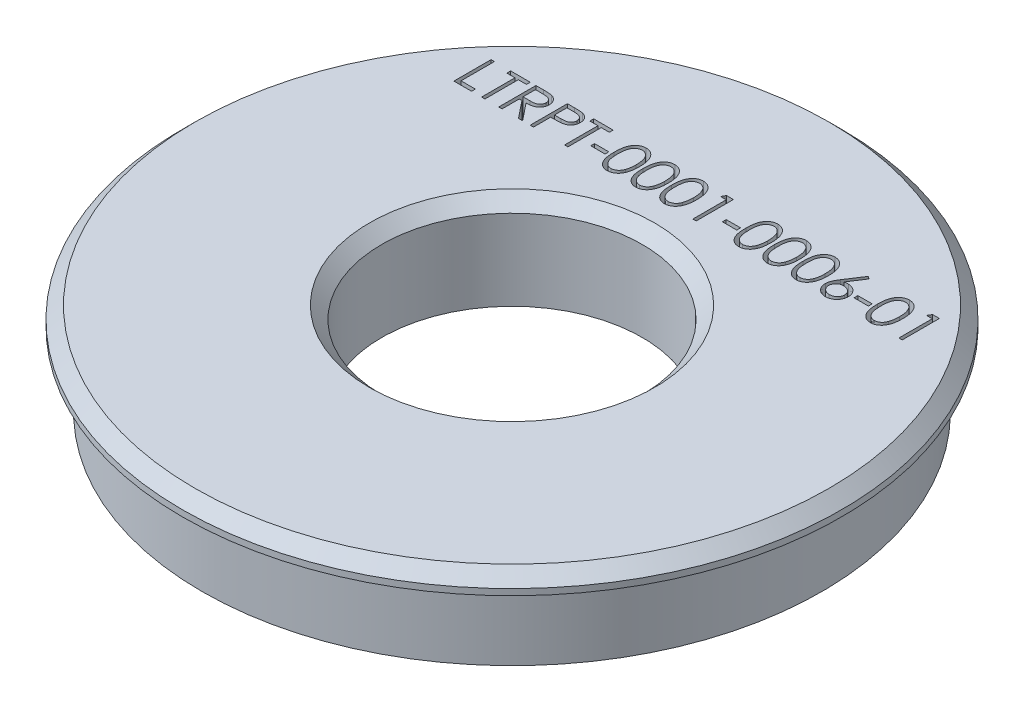
SolidWorks part; units mm, degrees
ref_plane "Front Plane" through (0, 0, 0) normal (0, 0, 1) x (1, 0, 0)
ref_plane "Top Plane" through (0, 0, 0) normal (0, 1, 0) x (1, 0, 0)
ref_plane "Right Plane" through (0, 0, 0) normal (1, 0, 0) x (0, 0, -1)
sketch "Sketch1" plane through (0, 0, 0) normal (0, 1, 0) x (1, 0, 0)
  circle A0 centre (0, 0) radius 25
  dimension "D1" = 50
extrude "Boss-Extrude1" add sketch "Sketch1" along normal blind 6
sketch "Sketch2" plane through (0, 6, 0) normal (0, 1, 0) x (1, 0, 0)
  circle A0 centre (0, 0) radius 10.5
  dimension "D1" = 21
extrude "Cut-Extrude1" cut sketch "Sketch2" against normal up to next
sketch "Sketch3" plane through (0, 6, 0) normal (0, 1, 0) x (1, 0, 0)
  circle A0 centre (0, 0) radius 19 construction
  circle A1 centre (0, 19) radius 2.5
  circle A2 centre (16.4545, 9.5) radius 2.5
  circle A3 centre (16.4545, -9.5) radius 2.5
  circle A4 centre (0, -19) radius 2.5
  circle A5 centre (-16.4545, -9.5) radius 2.5
  circle A6 centre (-16.4545, 9.5) radius 2.5
  point P17 (0, 0)
  dimension "D1" = 38
  dimension "D2" = 5
  dimension "D3" = 6
extrude "Cut-Extrude2" cut sketch "Sketch3" against normal through all
ref_axis "Axis1" through (0, 0, 0) along (0, 1, 0)
sketch "Sketch5" plane through (0, 6, 0) normal (0, 1, 0) x (1, 0, 0)
  circle A0 centre (0, 0) radius 20 construction
  circle A1 centre (20, 0) radius 1.25
  circle A2 centre (10, -17.3205) radius 1.25
  circle A3 centre (-10, -17.3205) radius 1.25
  circle A4 centre (-20, 0) radius 1.25
  circle A5 centre (-10, 17.3205) radius 1.25
  circle A6 centre (10, 17.3205) radius 1.25
  point P18 (0, 0)
  dimension "D1" = 40
  dimension "D2" = 2.5
  dimension "D3" = 6
extrude "Cut-Extrude3" cut sketch "Sketch5" against normal blind 4
sketch "Sketch6" plane through (0, 6, 0) normal (0, 1, 0) x (1, 0, 0)
  circle A0 centre (0, 0) radius 26.5767
  circle A1 centre (0, 0) radius 10.5 construction
  circle A2 centre (0, 0) radius 10.5
  circle A3 centre (10, -17.3205) radius 1.25 construction
  circle A4 centre (10, -17.3205) radius 1.25
  circle A5 centre (-10, -17.3205) radius 1.25 construction
  circle A6 centre (-10, -17.3205) radius 1.25
  circle A7 centre (-20, 0) radius 1.25 construction
  circle A8 centre (-10, 17.3205) radius 1.25 construction
  circle A9 centre (10, 17.3205) radius 1.25 construction
  circle A10 centre (20, 0) radius 1.25 construction
  circle A11 centre (-20, 0) radius 1.25
  circle A12 centre (-10, 17.3205) radius 1.25
  circle A13 centre (10, 17.3205) radius 1.25
  circle A14 centre (20, 0) radius 1.25
extrude "Boss-Extrude2" add sketch "Sketch6" along normal blind 1.5
sketch "Sketch7" plane through (0, 7.5, 0) normal (0, 1, 0) x (1, 0, 0)
  circle A0 centre (0, 19) radius 2.5 construction
  circle A1 centre (-16.4545, -9.5) radius 2.5 construction
  circle A2 centre (16.4545, -9.5) radius 2.5 construction
  circle A3 centre (0, 19) radius 2.5 construction
  circle A4 centre (-16.4545, -9.5) radius 2.5 construction
  circle A5 centre (16.4545, -9.5) radius 2.5 construction
  circle A6 centre (16.4545, -9.5) radius 4.5
  circle A7 centre (-16.4545, -9.5) radius 4.5
  circle A8 centre (0, 19) radius 4.5
  dimension "D1" = 9
extrude "Cut-Extrude4" cut sketch "Sketch7" against normal blind 5
sketch "Sketch8" plane through (0, 6, 0) normal (0, -1, 0) x (1, 0, 0)
  circle A0 centre (0, 19) radius 2.5 construction
  circle A1 centre (16.4545, -9.5) radius 2.5 construction
  circle A2 centre (0, 19) radius 2.5
  circle A3 centre (16.4545, -9.5) radius 2.5
  circle A5 centre (-16.4545, -9.5) radius 2.5
  circle A6 centre (-16.4545, -9.5) radius 2.5
  dimension "D1" = 0
extrude "Boss-Extrude3" add sketch "Sketch8" along normal blind 3
sketch "Sketch9" plane through (0, 7.5, 0) normal (0, 1, 0) x (1, 0, 0)
  circle A1 centre (0, 0) radius 10.5
  circle A2 centre (0, 0) radius 10.5 construction
  circle A22 centre (0, -19) radius 2.5 construction
  circle A23 centre (16.4545, -9.5) radius 2.5 construction
  circle A24 centre (16.4545, 9.5) radius 2.5 construction
  circle A25 centre (0, 19) radius 2.5 construction
  circle A26 centre (-16.4545, 9.5) radius 2.5 construction
  circle A27 centre (-16.4545, -9.5) radius 2.5 construction
  circle A28 centre (0, -19) radius 2.5
  circle A29 centre (16.4545, -9.5) radius 2.5
  circle A30 centre (16.4545, 9.5) radius 2.5
  circle A31 centre (0, 19) radius 2.5
  circle A32 centre (-16.4545, 9.5) radius 2.5
  circle A33 centre (-16.4545, -9.5) radius 2.5
  circle A34 centre (0, 0) radius 25 construction
  circle A35 centre (0, 0) radius 25
extrude "Boss-Extrude4" add sketch "Sketch9" against normal up to surface (5 mm away) up to face at (0, 2.5, -14.5)
sketch "Sketch10" plane through (0, 3, 0) normal (0, -1, 0) x (1, 0, 0)
  circle A0 centre (0, -19) radius 2.5 construction
  circle A1 centre (16.4545, 9.5) radius 2.5 construction
  circle A2 centre (-16.4545, 9.5) radius 2.5 construction
  circle A3 centre (0, -19) radius 2.5
  circle A4 centre (16.4545, 9.5) radius 2.5
  circle A5 centre (-16.4545, 9.5) radius 2.5
extrude "Boss-Extrude5" add sketch "Sketch10" against normal up to surface (4.5 mm away) up to face at (0, 7.5, 26.5767)
chamfer "Chamfer1" distance 1 angle 45 2 edges at (0, 7.5, 10.5) (0, 7.5, 26.5767)
sketch "Sketch11" plane through (0, 3, 0) normal (0, -1, 0) x (1, 0, 0)
  circle A0 centre (-16.4545, -9.5) radius 2.5 construction
  circle A1 centre (-16.4545, 9.5) radius 2.5 construction
  circle A2 centre (0, 19) radius 2.5 construction
  circle A3 centre (16.4545, 9.5) radius 2.5 construction
  circle A4 centre (16.4545, -9.5) radius 2.5 construction
  circle A5 centre (0, -19) radius 2.5 construction
  circle A6 centre (-16.4545, -9.5) radius 2.5
  circle A7 centre (-16.4545, 9.5) radius 2.5
  circle A8 centre (0, 19) radius 2.5
  circle A9 centre (16.4545, 9.5) radius 2.5
  circle A10 centre (16.4545, -9.5) radius 2.5
  circle A11 centre (0, -19) radius 2.5
extrude "Cut-Extrude5" cut sketch "Sketch11" against normal blind 2
sketch "Sketch12" plane through (0, 7.5, 0) normal (0, 1, 0) x (1, 0, 0)
  text T0 "LTRPT-0001-0006-01" font "Century Gothic" height 3
  point P1 (-8.238, 16.6281)
  point P2 (-10.1375, 15.5137)
  point P3 (0, 0)
  point P4 (0, 0)
  point P5 (-11.1684, 15.2523)
  point P6 (0, 0)
  point P7 (-9.9633, 15.4664)
  point P8 (-18.0997, 12.3659)
  point P9 (0, 0)
  point P10 (-17.3074, 13.21)
  point P11 (-15.9251, 13.3198)
extrude "Cut-Extrude6" cut sketch "Sketch12" against normal blind 2
equation "\"Output Pin Diameter\"= 38"
equation "\"D1@Sketch3\"=\"Output Pin Diameter\""
equation "\"Pin Diameter\"=5"
equation "\"D2@Sketch3\"=\"Pin Diameter\""
equation "\"Outer Diameter\"= 50"
equation "\"D1@Sketch1\"=\"Outer Diameter\""
equation "\"Inner Diameter\"= 21"
equation "\"D1@Sketch2\"=\"Inner Diameter\""
equation "\"Margin\"= 0.5"
